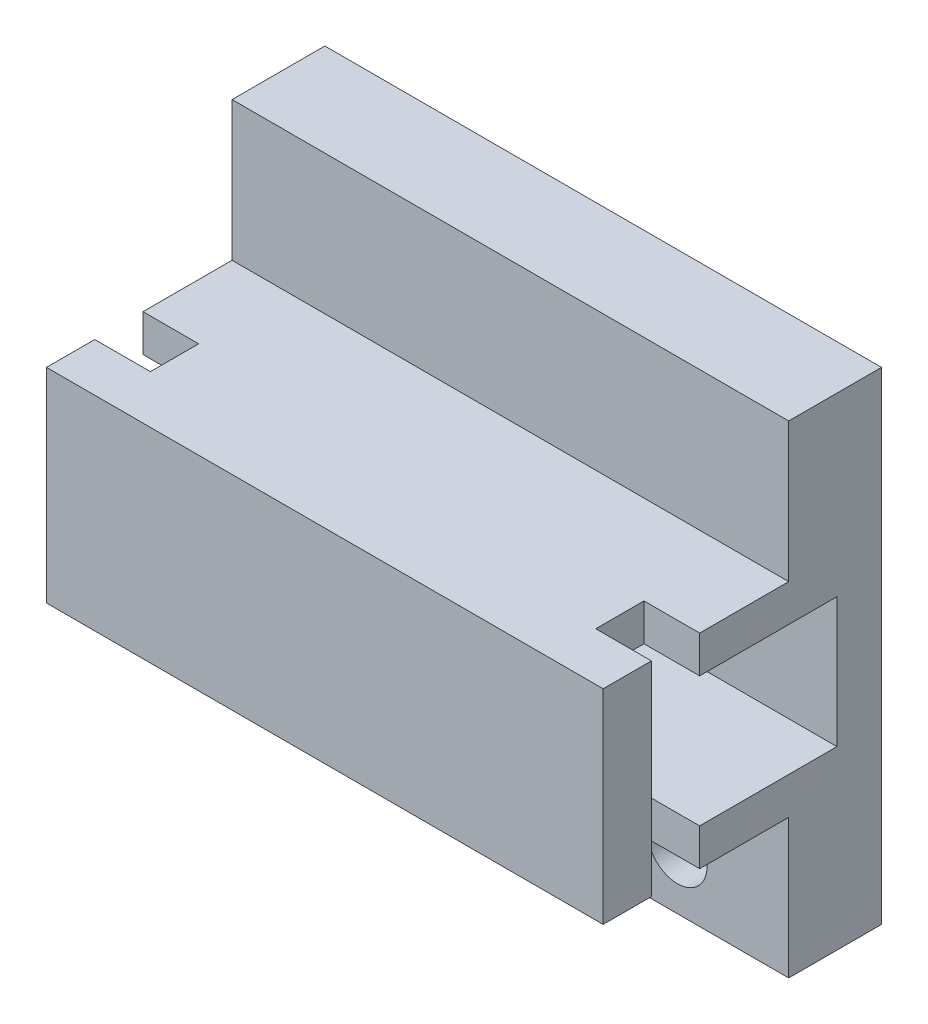
SolidWorks part; units mm, degrees
ref_plane "Спереди" through (0, 0, 0) normal (0, 0, 1) x (1, 0, 0)
ref_plane "Сверху" through (0, 0, 0) normal (0, 1, 0) x (1, 0, 0)
ref_plane "Справа" through (0, 0, 0) normal (1, 0, 0) x (0, 0, -1)
sketch "Эскиз1" plane through (0, 0, 0) normal (0, 0, 1) x (1, 0, 0)
  line L1 (-75, -65) -> (75, -65)
  line L2 (-75, -65) -> (-75, 65)
  line L3 (-75, 65) -> (75, 65)
  line L4 (75, -65) -> (75, 65)
  line L5 (-75, -65) -> (75, 65) construction
  line L6 (-75, 65) -> (75, -65) construction
  point P0 (0, 0)
  dimension "D1" = 130
  dimension "D2" = 150
extrude "Бобышка-Вытянуть1" add sketch "Эскиз1" along normal blind 25
sketch "Эскиз2" plane through (0, 0, 25) normal (0, 0, 1) x (1, 0, 0)
  line L0 (75, -65) -> (75, 65) construction
  line L1 (-75, -27.5) -> (75, -27.5)
  line L2 (-75, -27.5) -> (-75, 27.5)
  line L3 (-75, 27.5) -> (75, 27.5)
  line L4 (75, -27.5) -> (75, 27.5)
  line L5 (-75, -27.5) -> (75, 27.5) construction
  line L6 (-75, 27.5) -> (75, -27.5) construction
  point P0 (0, 0)
  dimension "D1" = 55
extrude "Бобышка-Вытянуть2" add sketch "Эскиз2" along normal blind 50
sketch "Эскиз4" plane through (0, 0, 25) normal (0, 0, 1) x (1, 0, 0)
  line L0 (75, -65) -> (75, -27.5) construction
  line L1 (-75, -65) -> (75, -65) construction
  circle A0 centre (45, -50) radius 8
  dimension "D1" = 30
  dimension "D2" = 15
  dimension "D3" = 16
extrude "Вырез-Вытянуть2" cut sketch "Эскиз4" against normal through all contours A0 region at (45, -50, 25)
sketch "Эскиз5" plane through (0, 0, 0) normal (1, 0, 0) x (0, 0, -1)
  line L0 (-75, -27.5) -> (-25, -65)
rib "Ребро1" sketch "Эскиз5" sketch "Эскиз5" thickness 20 extrusion direction parallel to sketch draft on no parameters "D1"=20
mirror "Зеркальное отражение1" about plane through (0, 0, 0) normal (1, 0, 0) of "Вырез-Вытянуть2"
sketch "Эскиз6" plane through (75, 0, 0) normal (1, 0, 0) x (0, 0, -1)
  line L0 (0, -65) -> (0, 65) construction
  line L1 (-12, -17.5) -> (-62, -17.5)
  line L2 (-12, -17.5) -> (-12, 17.5)
  line L3 (-12, 17.5) -> (-62, 17.5)
  line L4 (-62, -17.5) -> (-62, 17.5)
  line L5 (-12, -17.5) -> (-62, 17.5) construction
  line L6 (-12, 17.5) -> (-62, -17.5) construction
  line L7 (-75, -27.5) -> (-75, 27.5) construction
  point P0 (-37, 0)
  dimension "D1" = 12
  dimension "D2" = 13
  dimension "D3" = 35
extrude "Вырез-Вытянуть3" cut sketch "Эскиз6" against normal through all
sketch "Эскиз8" plane through (75, 0, 0) normal (1, 0, 0) x (0, 0, -1)
  line L0 (-75, 27.5) -> (-25, 27.5) construction
  line L1 (-62, 27.5) -> (-49, 27.5)
  line L2 (-62, 27.5) -> (-62, -27.5)
  line L3 (-62, -27.5) -> (-49, -27.5)
  line L4 (-49, 27.5) -> (-49, -27.5)
  line L5 (-75, -27.5) -> (-25, -27.5) construction
  line L6 (-62, 17.5) -> (-62, -17.5) construction
  dimension "D1" = 13
extrude "Вырез-Вытянуть4" cut sketch "Эскиз8" against normal blind 15
mirror "Зеркальное отражение2" about plane through (0, 0, 0) normal (1, 0, 0) of "Вырез-Вытянуть4"
